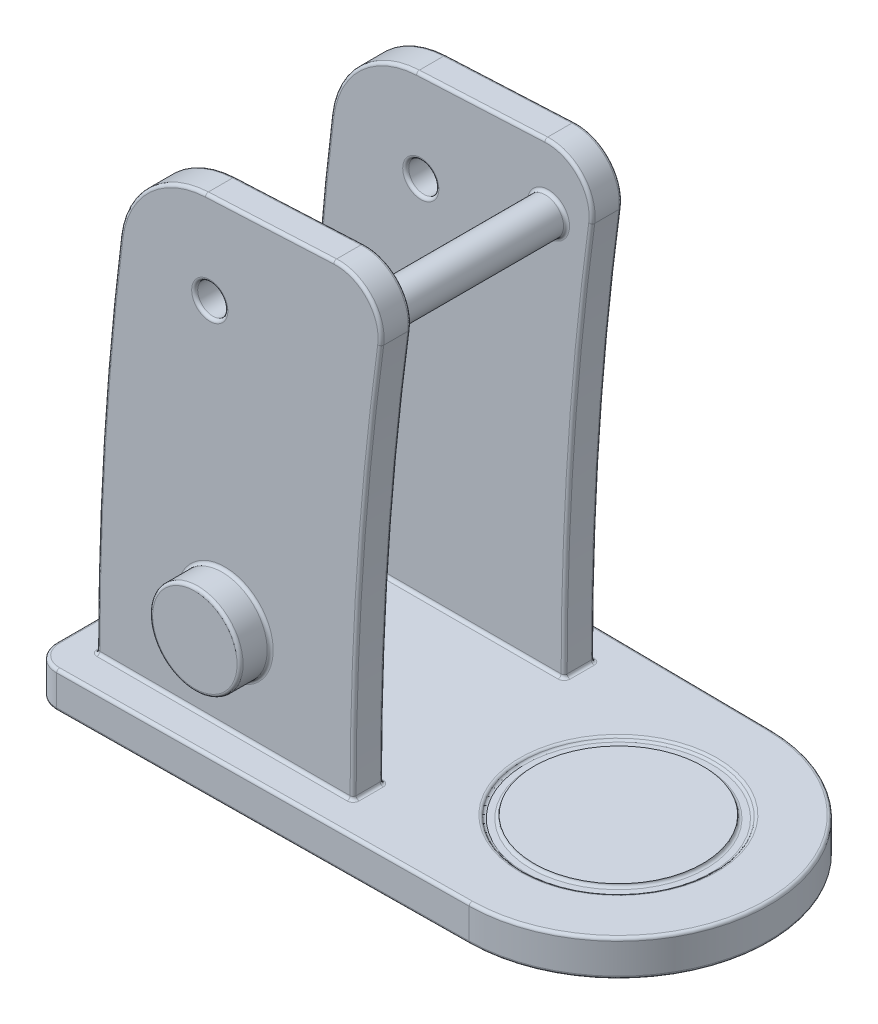
SolidWorks part; units mm, degrees
ref_plane "前视基准面" through (0, 0, 0) normal (0, 0, 1) x (1, 0, 0)
ref_plane "上视基准面" through (0, 0, 0) normal (0, 1, 0) x (1, 0, 0)
ref_plane "右视基准面" through (0, 0, 0) normal (1, 0, 0) x (0, 0, -1)
sketch "草图1" plane through (0, 0, 0) normal (0, 1, 0) x (1, 0, 0)
  line L0 (0, -43.4158) -> (0, 43.4158)
  line L1 (8.0838, 51.4154) -> (143.5235, 49.9973)
  line L2 (8.0838, -51.4154) -> (143.5235, -49.9973)
  arc A0 (143.5235, -49.9973) -> (143.5235, 49.9973) centre (143, 0) ccw
  arc A1 (0, -43.4158) -> (8.0838, -51.4154) centre (8, -43.4158) ccw
  arc A2 (0, 43.4158) -> (8.0838, 51.4154) centre (8, 43.4158) cw
  point P10 (0, 0)
  point P13 (0, 0)
  point P16 (0, 51.5)
  dimension "D2" = 100
  dimension "D4" = 8
  dimension "D1" = 51.5
  dimension "D3" = 143
extrude "凸台-拉伸1" add sketch "草图1" along normal blind 12
sketch "草图2" plane through (0, 12, 0) normal (0, 1, 0) x (1, 0, 0)
  circle A0 centre (143, 0) radius 32
  circle A1 centre (143, 0) radius 28
  dimension "D1" = 56
  dimension "D2" = 64
extrude "切除-拉伸1" cut sketch "草图2" against normal blind 1
fillet "圆角1" radius 1 2 edges at (143, 11, 32) (143, 11, 28)
sketch "草图5" plane through (0, 0, 0) normal (0, 0, 1) x (1, 0, 0)
  line L0 (8.0838, 12) -> (143.5235, 12) construction
  line L1 (46.0134, 161.9655) -> (88.5728, 164.0078)
  line L2 (95, 12) -> (10, 12)
  arc A0 (10, 12) -> (17.6818, 135.7113) centre (1010, 12) cw
  arc A1 (17.6818, 135.7113) -> (46.0134, 161.9655) centre (47.4513, 132) cw
  arc A2 (88.5728, 164.0078) -> (104.1544, 147) centre (89.2917, 149.025) cw
  arc A3 (104.1544, 147) -> (95, 12) centre (1095, 12) ccw
  dimension "D1" = 1000
  dimension "D2" = 30
  dimension "D3" = 15
  dimension "D4" = 1000
  dimension "D5" = 85
  dimension "D6" = 10
  dimension "D7" = 135
  dimension "D8" = 120
extrude "凸台-拉伸2" add sketch "草图5" against normal blind 10 from offset 40
extrude "凸台-拉伸3" add sketch "草图5<2>" along normal blind 10 from offset 40 offset against normal yes
sketch "草图5<2>" plane through (0, 0, 0) normal (0, 0, 1) x (1, 0, 0) same geometry as "草图5"
sketch "草图6" plane through (0, 0, 40) normal (0, 0, 1) x (1, 0, 0)
  line L0 (10, 12) -> (95, 12) construction
  circle A0 centre (52.5, 42) radius 15
  point P5 (52.5, 12)
  dimension "D1" = 30
  dimension "D2" = 30
extrude "凸台-拉伸4" add sketch "草图6" along normal blind 10
sketch "草图7" plane through (0, 0, 40) normal (0, 0, 1) x (1, 0, 0)
  circle A0 centre (89.7977, 143.0072) radius 6
  point P3 (0, 0)
  point P4 (89.7977, 143.0072)
  dimension "D1" = 12
extrude "凸台-拉伸5" add sketch "草图7" against normal up to surface (70 mm away) up to face at (59.4031, 106.9631, -30)
sketch "草图8" plane through (0, 0, -40) normal (0, 0, -1) x (-1, 0, 0)
  circle A0 centre (-47.4513, 132) radius 5
  dimension "D1" = 10
extrude "切除-拉伸2" cut sketch "草图8" against normal through all
fillet "圆角2" radius 1 48 edges at (97.2912, 79.655, 30) (100.3519, 159.1578, 30) (67.2931, 162.9866, 30) (27.0602, 154.0046, 30) (11.9223, 73.9748, 30) (83.7977, 143.0072, 30) (42.4513, 132, 30) (97.2912, 79.655, -40) (100.3519, 159.1578, -40) (67.2931, 162.9866, -40) (27.0602, 154.0046, -40) (11.9223, 73.9748, -40) (42.4513, 132, -40) (27.0602, 154.0046, -30) (67.2931, 162.9866, -30) (100.3519, 159.1578, -30) (97.2912, 79.655, -30) (11.9223, 73.9748, -30) (83.7977, 143.0072, -30) (42.4513, 132, -30) (27.0602, 154.0046, 40) (67.2931, 162.9866, 40) (100.3519, 159.1578, 40) (97.2912, 79.655, 40) (11.9223, 73.9748, 40) (37.5, 42, 40) (42.4513, 132, 40) (75.8036, 0, -50.7063) (2.3728, 0, -49.1022) (0, 0, 0) (2.3728, 0, 49.1022) (75.8036, 0, 50.7063) (193, 0, 0) (52.5, 12, -40) (10, 12, -35) (52.5, 12, -30) (95, 12, -35) (75.8036, 12, 50.7063) (2.3728, 12, 49.1022) (0, 12, 0) (2.3728, 12, -49.1022) (75.8036, 12, -50.7063) (193, 12, 0) (143, 12, 32) (10, 12, 35) (52.5, 12, 40) (95, 12, 35) (52.5, 12, 30)
fillet "圆角3" radius 1 1 edges at (67.5, 42, 50)
